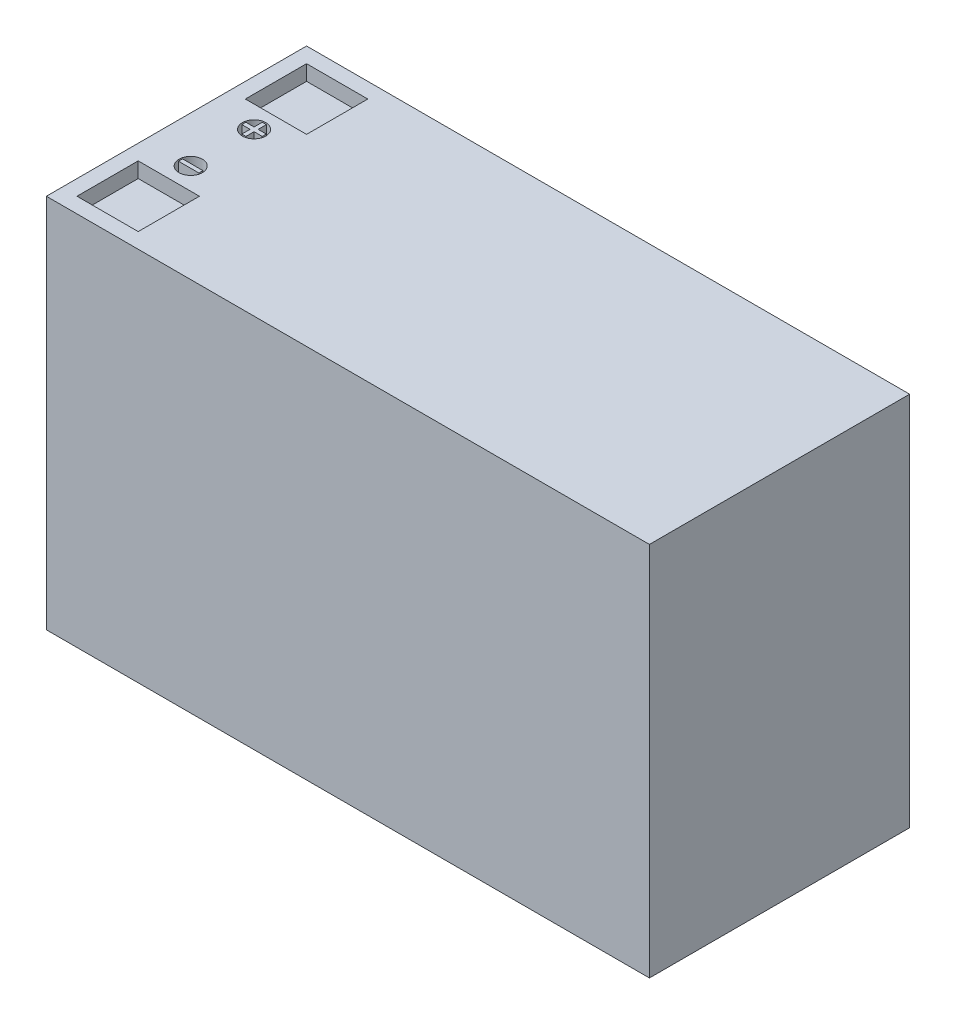
SolidWorks part; units mm, degrees
ref_plane "Front Plane" through (0, 0, 0) normal (0, 0, 1) x (1, 0, 0)
ref_plane "Top Plane" through (0, 0, 0) normal (0, 1, 0) x (1, 0, 0)
ref_plane "Right Plane" through (0, 0, 0) normal (1, 0, 0) x (0, 0, -1)
sketch "Sketch1" plane through (0, 0, 0) normal (0, 1, 0) x (1, 0, 0)
  line L1 (-71.4526, 38.2451) -> (78.6614, 38.2451)
  line L2 (-71.4526, 38.2451) -> (-71.4526, -26.5249)
  line L3 (-71.4526, -26.5249) -> (78.6614, -26.5249)
  line L4 (78.6614, 38.2451) -> (78.6614, -26.5249)
  dimension "D1" = 64.77
  dimension "D2" = 150.114
extrude "Boss-Extrude1" add sketch "Sketch1" along normal blind 93.472
sketch "Sketch2" plane through (0, 93.472, 0) normal (0, 1, 0) x (1, 0, 0)
  line L0 (-60.0226, -4.9404) -> (-60.0226, -4.9349)
  line L1 (-71.4526, 5.8601) -> (58.9596, 5.8601) construction
  line L2 (-67.6426, -22.7149) -> (-52.4026, -22.7149)
  line L3 (-71.4526, 38.2451) -> (-71.4526, -26.5249) construction
  line L4 (-60.0226, -1.5186) -> (-57.4826, -1.5186)
  line L5 (-60.0226, -1.5186) -> (-62.5626, -1.5186)
  line L6 (-67.6426, -22.7149) -> (-67.6426, -7.4749)
  line L7 (-67.6426, -7.4749) -> (-52.4026, -7.4749)
  line L8 (-52.4026, -22.7149) -> (-52.4026, -7.4749)
  line L9 (-62.5626, -1.5186) -> (-62.5626, -2.5346)
  line L10 (-62.5626, -2.5346) -> (-57.4826, -2.5346)
  line L11 (-57.4826, -1.5186) -> (-57.4826, -2.5346)
  line L12 (-57.4826, 13.2388) -> (-57.4826, 14.2548)
  line L13 (-59.516, 14.2548) -> (-57.4826, 14.2548)
  line L14 (-62.5626, 13.2388) -> (-62.5626, 14.2548)
  line L15 (-52.4026, 34.4351) -> (-52.4026, 19.1951)
  line L16 (-67.6426, 19.1951) -> (-52.4026, 19.1951)
  line L17 (-67.6426, 34.4351) -> (-67.6426, 19.1951)
  line L18 (-60.532, 13.2388) -> (-62.5626, 13.2388)
  line L19 (-59.516, 13.2388) -> (-57.4826, 13.2388)
  line L20 (-67.6426, 34.4351) -> (-52.4026, 34.4351)
  line L21 (-60.0226, 16.6607) -> (-60.0226, 16.6551)
  line L22 (-58.4993, 14.2548) -> (-59.516, 14.2548)
  line L23 (-60.532, 14.2548) -> (-60.532, 16.2868)
  line L24 (-62.5626, 14.2548) -> (-60.532, 14.2548)
  line L25 (-60.532, 16.2868) -> (-59.516, 16.2868)
  line L26 (-59.516, 16.2868) -> (-59.516, 14.2548)
  line L27 (-60.532, 13.2388) -> (-60.532, 11.2068)
  line L28 (-60.532, 11.2068) -> (-59.516, 11.2068)
  line L29 (-59.516, 13.2388) -> (-59.516, 11.2068)
  circle A0 centre (-60.0226, -2.0266) radius 2.9139
  circle A1 centre (-60.0226, 13.7468) radius 2.9139
  dimension "D1" = 15.24
  dimension "D2" = 0.508
  dimension "D3" = 15.24
  dimension "D4" = 2.9083
  dimension "D5" = 2.032
  dimension "D6" = 2.54
  dimension "D7" = 2.54
  dimension "D8" = 1.016
  dimension "D9" = 1.016
  dimension "D10" = 5.08
  dimension "D11" = 3.048
extrude "Cut-Extrude1" cut sketch "Sketch2" against normal blind 3.81 contours L20 L17 L16 L15 | L2 L8 L7 L6 | A0 L4 L11 L10 L9 L5 | A1 L19 L29 L28 L27 L18 L14 L24 L23 L25 L26 L13 L12 region at (-60.0226, 93.472, 15.0949) region at (-60.0226, 93.472, -26.8151) region at (-58.0205, 93.472, 4.0287) region at (-62.0248, 93.472, -11.7447)
